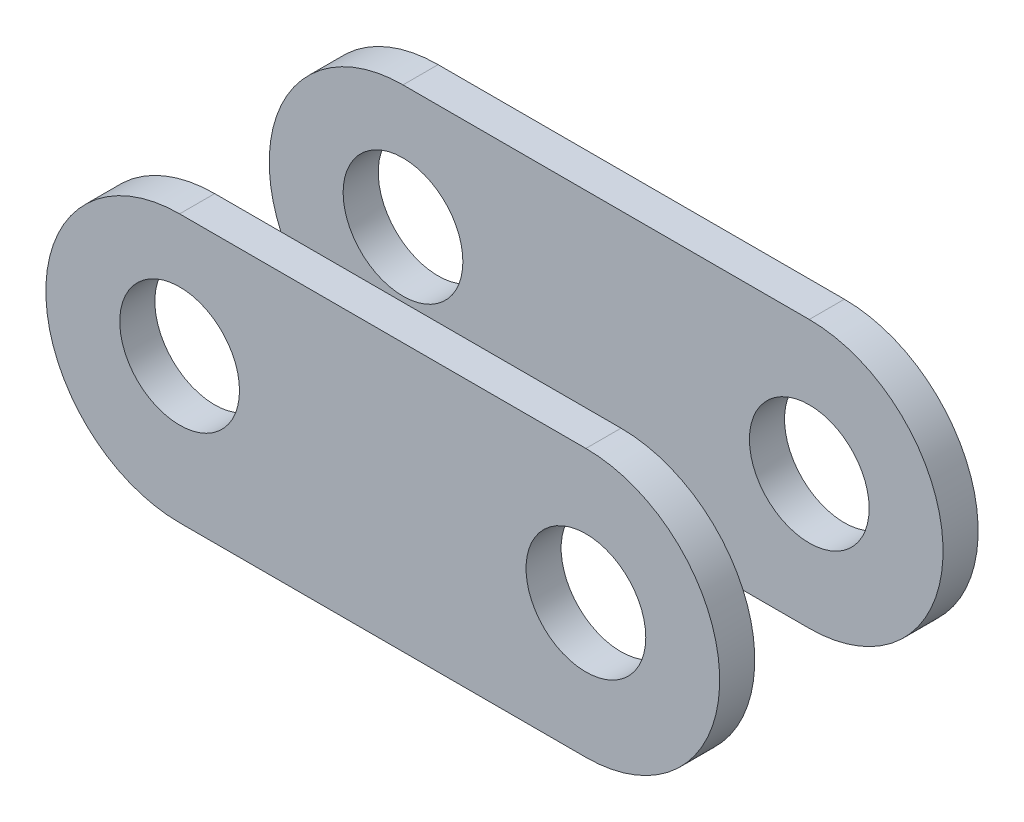
SolidWorks part; units mm, degrees
ref_plane "Front Plane" through (0, 0, 0) normal (0, 0, 1) x (1, 0, 0)
ref_plane "Top Plane" through (0, 0, 0) normal (0, 1, 0) x (1, 0, 0)
ref_plane "Right Plane" through (0, 0, 0) normal (1, 0, 0) x (0, 0, -1)
sketch "Sketch2" plane through (0, 0, 0) normal (0, 0, 1) x (1, 0, 0)
  line L0 (-9.4658, 0) -> (3.031, 0) construction
  line L1 (3.1153, 0) -> (-3.1153, 0) construction
  line L2 (-9.4658, 4.1148) -> (3.031, 4.1148)
  line L3 (-9.4658, -4.1148) -> (3.031, -4.1148)
  arc A0 (-9.4658, 4.1148) -> (-9.4658, -4.1148) centre (-9.4658, 0) ccw
  arc A1 (3.031, -4.1148) -> (3.031, 4.1148) centre (3.031, 0) ccw
  circle A2 centre (-9.4658, 0.3281) radius 1.8415
  circle A3 centre (3.031, 0) radius 1.8415
  point P5 (-3.2174, 0)
  dimension "D1" = 3.683
  dimension "D2" = 3.683
  dimension "D3" = 12.4968
  dimension "D4" = 8.2296
extrude "Boss-Extrude1" add sketch "Sketch2" along normal blind 3.9751 and the other way blind 3.9751
sketch "Sketch3" plane through (0, 4.1148, 0) normal (0, 1, 0) x (1, 0, 0)
  line L0 (-13.5806, 3.9751) -> (-13.5806, -3.9751) construction
  line L1 (-13.5806, 2.8956) -> (7.1458, 2.8956)
  line L2 (-13.5806, 2.8956) -> (-13.5806, -2.8956)
  line L3 (-13.5806, -2.8956) -> (7.1458, -2.8956)
  line L4 (7.1458, 2.8956) -> (7.1458, -2.8956)
  line L5 (7.1458, -3.9751) -> (7.1458, 3.9751) construction
  line L6 (3.031, -3.9751) -> (-9.4658, -3.9751) construction
  dimension "D1" = 5.7912
  dimension "D2" = 1.0795
extrude "Cut-Extrude1" cut sketch "Sketch3" against normal through all
sketch "Sketch6" [suppressed] plane through (0, 4.1148, 0) normal (0, 1, 0) x (1, 0, 0)
  line L0 (-13.5806, 3.9751) -> (-13.5806, -3.9751) construction
  line L1 (-13.5806, 1.6891) -> (7.1458, 1.6891)
  line L2 (-13.5806, 1.6891) -> (-13.5806, -1.6891)
  line L3 (-13.5806, -1.6891) -> (7.1458, -1.6891)
  line L4 (7.1458, 1.6891) -> (7.1458, -1.6891)
  line L5 (7.1458, -3.9751) -> (7.1458, 3.9751) construction
  line L6 (3.031, 3.9751) -> (-9.4658, 3.9751) construction
  line L7 (3.031, -3.9751) -> (-9.4658, -3.9751) construction
  dimension "D1" = 2.286
  dimension "D2" = 2.286
extrude "Cut-Extrude2" [suppressed] cut sketch "Sketch6" against normal through all
sketch "Sketch7" [suppressed] plane through (0, 4.1148, 0) normal (0, 1, 0) x (1, 0, 0)
  line L0 (-13.5806, 3.9751) -> (-13.5806, 1.6891) construction
  line L1 (7.1458, 3.9751) -> (-13.5806, 3.9751)
  line L2 (7.1458, 3.9751) -> (7.1458, 2.8321)
  line L3 (7.1458, 2.8321) -> (-13.5806, 2.8321)
  line L4 (-13.5806, 3.9751) -> (-13.5806, 2.8321)
extrude "Cut-Extrude3" [suppressed] cut sketch "Sketch7" against normal through all
sketch "Sketch8" [suppressed] plane through (0, 4.1148, 0) normal (0, 1, 0) x (1, 0, 0)
  line L0 (-13.5806, -1.6891) -> (-13.5806, -3.9751) construction
  line L1 (7.1458, -3.9751) -> (-13.5806, -3.9751)
  line L2 (7.1458, -3.9751) -> (7.1458, -2.8321)
  line L3 (7.1458, -2.8321) -> (-13.5806, -2.8321)
  line L4 (-13.5806, -3.9751) -> (-13.5806, -2.8321)
  dimension "D1" = 1.143
extrude "Cut-Extrude4" [suppressed] cut sketch "Sketch8" against normal through all
equation "\"D1@Sketch2\"= \"D2@Sketch2\""
equation "\"D2@Sketch6\"= \"D1@Sketch6\""
